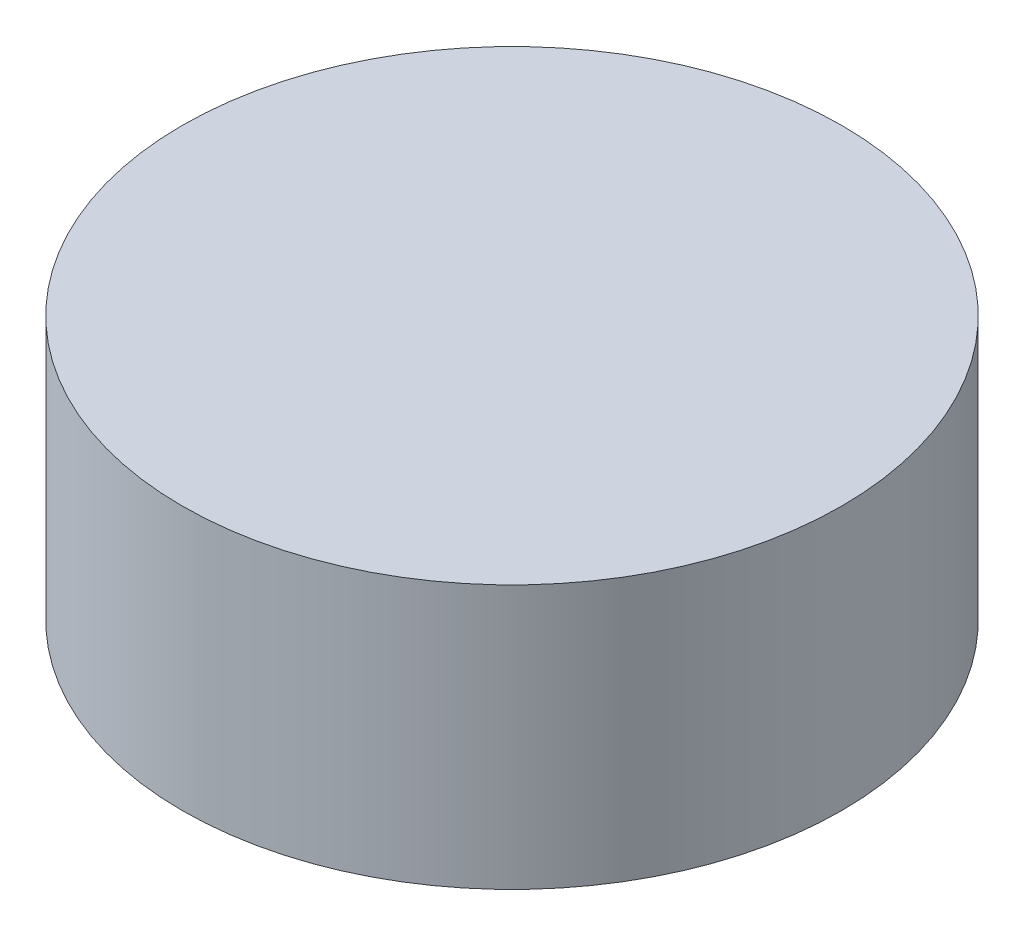
SolidWorks part; units mm, degrees
material "6061 합금"
ref_plane "정면" through (0, 0, 0) normal (0, 0, 1) x (1, 0, 0)
ref_plane "윗면" through (0, 0, 0) normal (0, 1, 0) x (1, 0, 0)
ref_plane "우측면" through (0, 0, 0) normal (1, 0, 0) x (0, 0, -1)
sketch "스케치1" plane through (0, 0, 0) normal (0, 1, 0) x (1, 0, 0)
  circle A0 centre (0, 0) radius 35
  circle A1 centre (0, 0) radius 30
  dimension "D1" = 70
  dimension "D2" = 60
extrude "보스-돌출1" add sketch "스케치1" along normal mid plane 28
extrude "보스-돌출2" add sketch "스케치1<2>" along normal blind 5 from surface contours A1 region at (0, 0, 0) starting at face at (0, -14, 35)
sketch "스케치1<2>" plane through (0, 0, 0) normal (0, 1, 0) x (1, 0, 0) same geometry as "스케치1"
extrude "보스-돌출3" add sketch "스케치1<3>" against normal blind 5 from surface contours A1 region at (0, 0, 0) starting at face at (0, 14, 35)
sketch "스케치1<3>" plane through (0, 0, 0) normal (0, 1, 0) x (1, 0, 0) same geometry as "스케치1"
